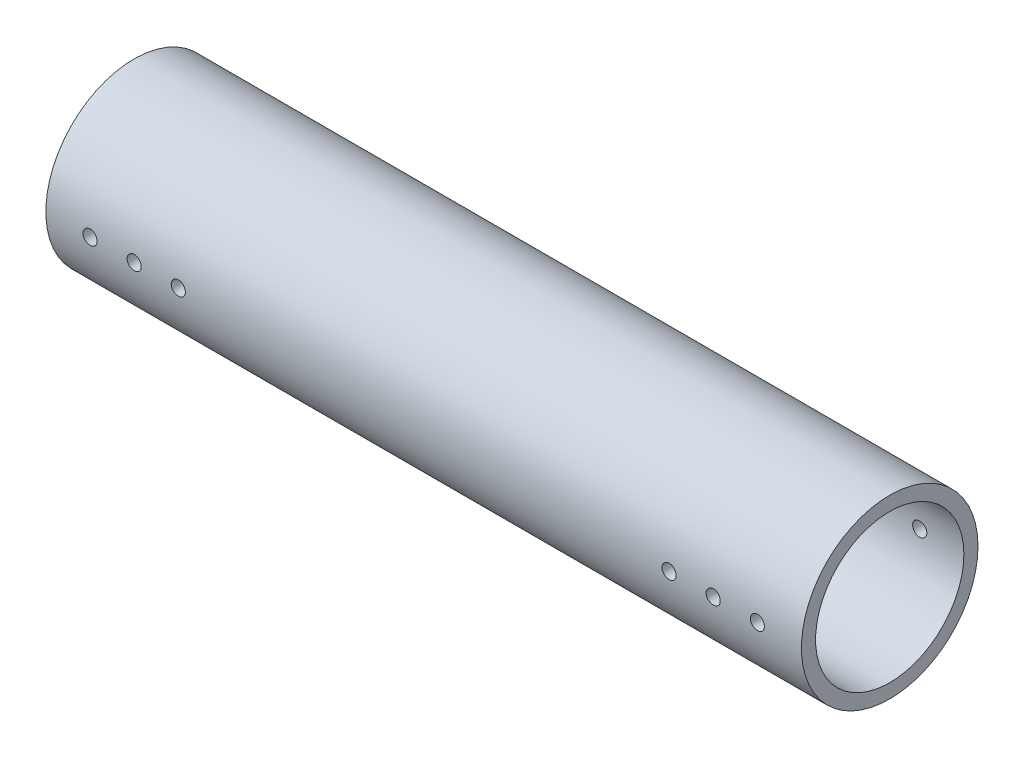
SolidWorks part; units mm, degrees
material "Zoltek Panex 33"
ref_plane "Спереди" through (0, 0, 0) normal (0, 0, 1) x (1, 0, 0)
ref_plane "Сверху" through (0, 0, 0) normal (0, 1, 0) x (1, 0, 0)
ref_plane "Справа" through (0, 0, 0) normal (1, 0, 0) x (0, 0, -1)
other "Configuration Table"
sketch "Эскиз2" plane through (0, 0, 0) normal (1, 0, 0) x (0, 0, -1)
  circle A0 centre (0, 0) radius 25
  circle A1 centre (0, 0) radius 21
  dimension "D1" = 50
  dimension "D2" = 42
extrude "Бобышка-Вытянуть2" add sketch "Эскиз2" along normal blind 214
ref_plane "Плоскость1" through (0, 0, 25) normal (0, 0, 1) x (1, 0, 0)
sketch "Эскиз4" plane through (0, 0, 25) normal (0, 0, 1) x (1, 0, 0)
  line L0 (0, -25) -> (214, -25) construction
  line L1 (214, -25) -> (214, 25) construction
  circle A0 centre (12.5, 0) radius 2
  circle A1 centre (201.5, 0) radius 2
  circle A2 centre (25, 0) radius 2
  circle A3 centre (37.5, 0) radius 2
  circle A4 centre (189, 0) radius 2
  circle A5 centre (176.5, 0) radius 2
  dimension "D1" = 4
  dimension "D4" = 4
  dimension "D6" = 4
  dimension "D8" = 4
  dimension "D10" = 4
  dimension "D11" = 4
  dimension "D2" = 12.5
  dimension "D3" = 25
  dimension "D5" = 12.5
  dimension "D7" = 12.5
  dimension "D9" = 12.5
  dimension "15" = 12.5
  dimension "D12" = 12.5
extrude "Вырез-Вытянуть2" cut sketch "Эскиз4" against normal through all and the other way blind 10 contours A0 | A1 | A2 | A3 | A5 | A4
equation "\"Diameter\"= 50мм"
equation "\"D1@Эскиз2\"= \"Diameter\""
equation "\"Length\"= 214мм"
equation "\"Thickness\"= 4мм"
equation "\"D1@Бобышка-Вытянуть2\"= \"Length\""
equation "\"D2@Эскиз2\" = \"Diameter\" - \"Thickness\" * 2"
equation "\"D4@Эскиз4\"=\"D1@Эскиз4\""
equation "\"D5@Эскиз4\"=\"D2@Эскиз4\""
equation "\"D3@Эскиз4\"=\"Diameter\"/2"
equation "\"D6@Эскиз4\"=\"D1@Эскиз4\""
equation "\"D8@Эскиз4\"=\"D6@Эскиз4\""
equation "\"D10@Эскиз4\"=\"D4@Эскиз4\""
equation "\"D11@Эскиз4\"=\"D4@Эскиз4\""
equation "\"D9@Эскиз4\"=\"D7@Эскиз4\""
